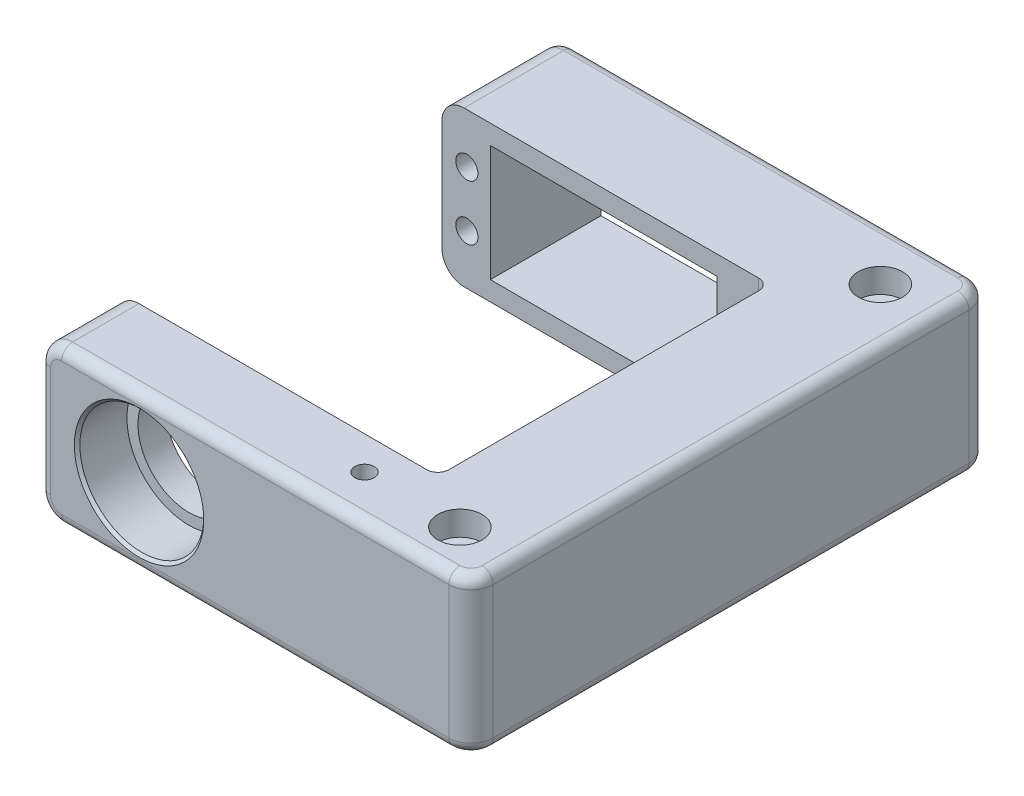
SolidWorks part; units mm, degrees
ref_plane "Top Plane" through (0, 0, 0) normal (0, 0, 1) x (1, 0, 0)
ref_plane "Right Plane" through (0, 0, 0) normal (0, 1, 0) x (1, 0, 0)
ref_plane "Front Plane" through (0, 0, 0) normal (1, 0, 0) x (0, 0, -1)
sketch "Sketch1" plane through (0, 0, 0) normal (0, 0, 1) x (1, 0, 0)
  line L0 (-10, 0) -> (30, 0) construction
  line L1 (-10, 10) -> (30, 10) construction
  line L2 (-10, 10) -> (-10, -10) construction
  line L3 (-10, -10) -> (30, -10) construction
  line L4 (30, 10) -> (30, -10) construction
  line L5 (-10, 10) -> (-17.25, 10) construction
  line L6 (-17.25, 10) -> (-17.25, -10) construction
  line L7 (-17.25, -10) -> (-10, -10) construction
  line L8 (10, 10) -> (10, -10) construction
  line L9 (37.25, -10) -> (30, -10) construction
  line L10 (37.25, 10) -> (37.25, -10) construction
  line L11 (30, 10) -> (37.25, 10) construction
  line L12 (40, 14) -> (40, -14) construction
  line L13 (-19.25, 14) -> (60, 14)
  line L14 (-19.25, 14) -> (-19.25, -14)
  line L15 (-19.25, -14) -> (60, -14)
  line L16 (60, 14) -> (60, -14)
  circle A0 centre (0, 0) radius 11 construction
  circle A1 centre (0, 0) radius 4 construction
  circle A2 centre (-14.75, 5) radius 2 construction
  circle A3 centre (-14.75, -5) radius 2 construction
  circle A4 centre (34.75, -5) radius 2 construction
  circle A5 centre (34.75, 5) radius 2 construction
  dimension "D1" = 22
  dimension "D2" = 8
  dimension "D12" = 4
  dimension "D3" = 40
  dimension "D4" = 20
  dimension "D5" = 54.5
  dimension "D6" = 37.25
  dimension "D7" = 20
  dimension "D8" = 40
  dimension "D9" = 14
  dimension "D10" = 14
  dimension "D11" = 2
  dimension "D13" = 10
  dimension "D14" = 49.5
extrude "Boss-Extrude1" add sketch "Sketch1" along normal blind 20
sketch "Sketch2" plane through (0, 0, 20) normal (0, 0, 1) x (1, 0, 0)
  line L1 (40, 14) -> (60, 14)
  line L2 (40, 14) -> (40, -14)
  line L3 (40, -14) -> (60, -14)
  line L4 (60, 14) -> (60, -14)
extrude "Boss-Extrude2" add sketch "Sketch2" along normal blind 60
sketch "Sketch3" plane through (0, 0, 80) normal (0, 0, 1) x (1, 0, 0)
  line L0 (-19.25, -14) -> (60, -14) construction
  line L1 (60, 14) -> (-18, 14)
  line L2 (60, 14) -> (60, -14)
  line L3 (60, -14) -> (-18, -14)
  line L4 (-18, 14) -> (-18, -14)
  dimension "D1" = 18
extrude "Boss-Extrude3" add sketch "Sketch3" along normal blind 14
sketch "Sketch4" plane through (0, 0, 20) normal (0, 0, 1) x (1, 0, 0)
  line L8 (-10.5, -10.5) -> (30.5, -10.5)
  line L9 (30.5, -10.5) -> (30.5, 10.5)
  line L10 (30.5, 10.5) -> (-10.5, 10.5)
  line L11 (-10.5, 10.5) -> (-10.5, -10.5)
  line L12 (-10.5, -10.5) -> (30.5, -10.5)
  line L13 (30.5, -10.5) -> (30.5, 10.5)
  line L14 (30.5, 10.5) -> (-10.5, 10.5)
  line L15 (-10.5, 10.5) -> (-10.5, -10.5)
  dimension "D1" = 0.5
extrude "Cut-Extrude1" cut sketch "Sketch4" against normal through all
sketch "Sketch5" plane through (0, 0, 20) normal (0, 0, 1) x (1, 0, 0)
  circle A0 centre (34.75, -5) radius 2 construction
  circle A1 centre (34.75, 5) radius 2 construction
  circle A2 centre (-14.75, -5) radius 2 construction
  circle A3 centre (-14.75, 5) radius 2 construction
  circle A4 centre (34.75, -5) radius 2
  circle A5 centre (34.75, 5) radius 2
  circle A6 centre (-14.75, -5) radius 2
  circle A7 centre (-14.75, 5) radius 2
extrude "Cut-Extrude2" cut sketch "Sketch5" against normal through all
sketch "Sketch6" plane through (0, 0, 0) normal (0, 0, -1) x (-1, 0, 0)
  line L0 (-10, 10.5) -> (-10, -10.5) construction
  line L1 (-34.75, 8.4641) -> (-37.75, 6.7321)
  line L2 (-37.75, 6.7321) -> (-37.75, 3.2679)
  line L3 (-37.75, 3.2679) -> (-34.75, 1.5359)
  line L4 (-34.75, 1.5359) -> (-31.75, 3.2679)
  line L5 (-31.75, 3.2679) -> (-31.75, 6.7321)
  line L6 (-31.75, 6.7321) -> (-34.75, 8.4641)
  line L7 (-34.75, -1.5359) -> (-37.75, -3.2679)
  line L8 (-37.75, -3.2679) -> (-37.75, -6.7321)
  line L9 (-37.75, -6.7321) -> (-34.75, -8.4641)
  line L10 (-34.75, -8.4641) -> (-31.75, -6.7321)
  line L11 (-31.75, -6.7321) -> (-31.75, -3.2679)
  line L12 (-31.75, -3.2679) -> (-34.75, -1.5359)
  line L13 (-30.5, 10.5) -> (10.5, 10.5) construction
  line L14 (10.5, -10.5) -> (-30.5, -10.5) construction
  line L15 (11.75, -3.2679) -> (14.75, -1.5359)
  line L16 (11.75, -6.7321) -> (11.75, -3.2679)
  line L17 (14.75, -8.4641) -> (11.75, -6.7321)
  line L18 (17.75, -6.7321) -> (14.75, -8.4641)
  line L19 (17.75, -3.2679) -> (17.75, -6.7321)
  line L20 (14.75, -1.5359) -> (17.75, -3.2679)
  line L21 (11.75, 6.7321) -> (14.75, 8.4641)
  line L22 (11.75, 3.2679) -> (11.75, 6.7321)
  line L23 (14.75, 1.5359) -> (11.75, 3.2679)
  line L24 (17.75, 3.2679) -> (14.75, 1.5359)
  line L25 (17.75, 6.7321) -> (17.75, 3.2679)
  line L26 (14.75, 8.4641) -> (17.75, 6.7321)
  circle A0 centre (-34.75, 5) radius 3 construction
  circle A1 centre (-34.75, -5) radius 3 construction
  circle A2 centre (14.75, -5) radius 3 construction
  circle A3 centre (14.75, 5) radius 3 construction
  dimension "D1" = 6
extrude "Cut-Extrude3" cut sketch "Sketch6" against normal offset from surface (14 mm away) 6 up to face at (36.75, 5, 20)
sketch "Sketch7" plane through (0, 0, 94) normal (0, 0, 1) x (1, 0, 0)
  circle A2 centre (0, 0) radius 11.2
  circle A3 centre (0, 0) radius 11.2
  dimension "D1" = 0.2
extrude "Cut-Extrude4" cut sketch "Sketch7" against normal blind 9
sketch "Sketch8" plane through (0, 0, 85) normal (0, 0, 1) x (1, 0, 0)
  circle A0 centre (0, 0) radius 9.2
  circle A1 centre (0, 0) radius 11.2 construction
  dimension "D1" = 2
extrude "Cut-Extrude5" cut sketch "Sketch8" against normal up to next
sketch "Sketch12" plane through (0, 14, 0) normal (0, 1, 0) x (1, 0, 0)
  line L0 (60, 0) -> (-19.25, 0) construction
  line L1 (60, -94) -> (60, 0) construction
  line L2 (60, -94) -> (-18, -94) construction
  circle A0 centre (50, -10) radius 2 construction
  circle A1 centre (50, -10) radius 3.75 construction
  circle A2 centre (50, -86) radius 2 construction
  circle A3 centre (50, -86) radius 3.75 construction
  dimension "D1" = 4
  dimension "D2" = 7.5
  dimension "D5" = 8
  dimension "D3" = 10
  dimension "D4" = 10
  dimension "D6" = 10
hole_wizard "CBORE for M4 Hex Socket Head Cap Screw1" positions "Sketch13" profile "Sketch14" counterbore size "M4" standard "ISO" end condition through all
sketch "Sketch13" plane through (0, 14, 0) normal (0, 1, 0) x (1, 0, 0)
  point P2 (50, -10)
  point P7 (50, -86)
sketch "Sketch14" plane through (50, 14, 10) normal (1, 0, 0) x (0, 0, 1)
  line L0 (0, 0) -> (0, 28)
  line L1 (0, 28) -> (2.15, 28)
  line L3 (2.15, 28) -> (2.15, 4.4)
  line L4 (2.15, 4.4) -> (4, 4.4)
  line L5 (4, 4.4) -> (4, 0)
  line L7 (4, 0) -> (0, 0)
  line L11 (0, -6.35) -> (0, 107.95) construction
  dimension "Thru Hole Dia." = 4.3
  dimension "Thru Hole Depth" = 28
  dimension "C'Bore Dia." = 8
  dimension "C'Bore Depth" = 4.4
sketch "Sketch15" plane through (0, 14, 0) normal (0, 1, 0) x (1, 0, 0)
  line L0 (32.75, -86) -> (50, -86) construction
  circle A0 centre (32.75, -86) radius 1.75
  point P2 (0, 0)
  point P4 (0, 0)
  dimension "D1" = 17.25
  dimension "D2" = 3.5
extrude "Cut-Extrude6" cut sketch "Sketch15" against normal through all
sketch "Sketch16" plane through (0, -14, 0) normal (0, -1, 0) x (1, 0, 0)
  line L1 (31.0179, 89) -> (29.2859, 86)
  line L2 (29.2859, 86) -> (31.0179, 83)
  line L3 (31.0179, 83) -> (34.4821, 83)
  line L4 (34.4821, 83) -> (36.2141, 86)
  line L5 (36.2141, 86) -> (34.4821, 89)
  line L6 (34.4821, 89) -> (31.0179, 89)
  circle A0 centre (32.75, 86) radius 3 construction
  dimension "D1" = 6
extrude "Cut-Extrude7" cut sketch "Sketch16" against normal blind 5
fillet "Fillet6" radius 0.5 7 edges at (32.75, -9, 84.25) (30.1519, -9, 84.5) (32.75, -9, 83) (35.3481, -9, 84.5) (35.3481, -9, 87.5) (32.75, -9, 89) (30.1519, -9, 87.5)
fillet "Fillet1" radius 4 4 edges at (-18, -14, 87) (-18, 14, 87) (-19.25, -14, 10) (-19.25, 14, 10)
fillet "Fillet3" radius 4 2 edges at (60, 0, 0) (60, 0, 94)
fillet "Fillet4" radius 2 2 edges at (40, 0, 20) (40, 0, 80)
fillet "Fillet5" radius 2 16 edges at (58.8284, -14, 92.8284) (21, -14, 94) (-16.8284, -12.8284, 94) (-18, 0, 94) (-16.8284, 12.8284, 94) (21, 14, 94) (58.8284, 14, 92.8284) (60, 14, 47) (58.8284, 14, 1.1716) (20.375, 14, 0) (-18.0784, 12.8284, 0) (-19.25, 0, 0) (-18.0784, -12.8284, 0) (20.375, -14, 0) (58.8284, -14, 1.1716) (60, -14, 47)
chamfer "Chamfer1" distance 0.5 angle 45 1 edges at (11.2, 0, 94)
